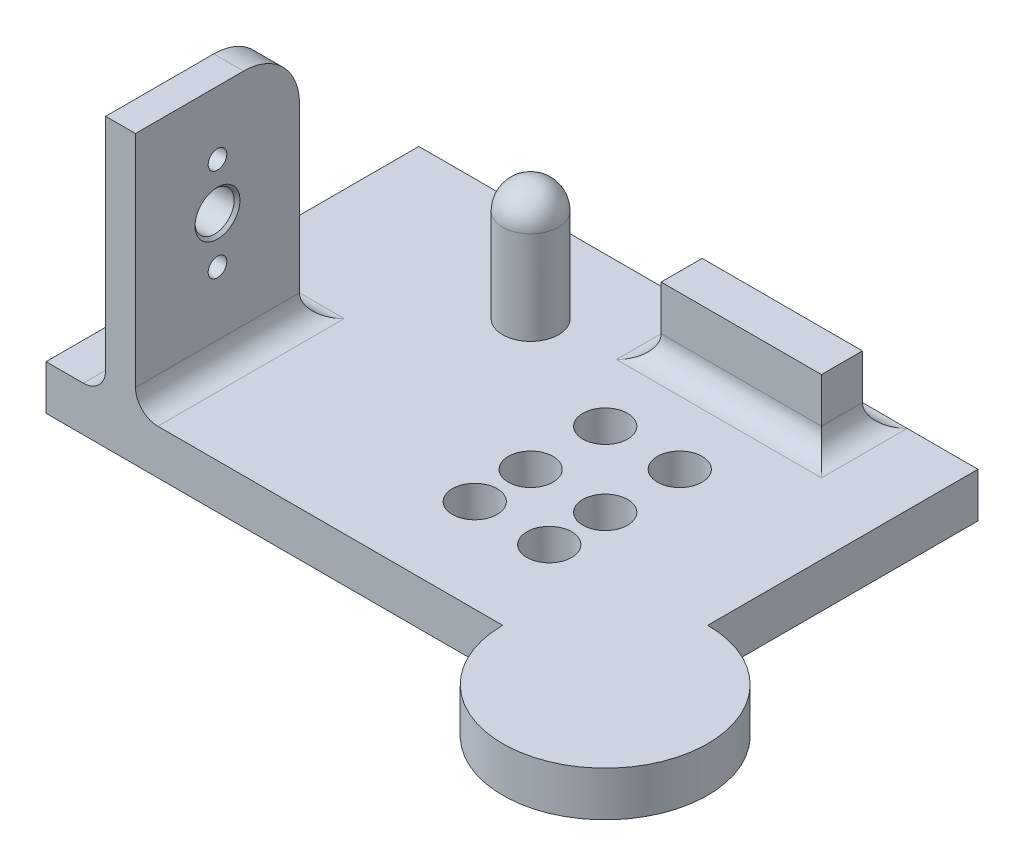
SolidWorks part; units mm, degrees
ref_plane "Front Plane" through (0, 0, 0) normal (0, 0, 1) x (1, 0, 0)
ref_plane "Top Plane" through (0, 0, 0) normal (0, 1, 0) x (1, 0, 0)
ref_plane "Right Plane" through (0, 0, 0) normal (1, 0, 0) x (0, 0, -1)
sketch "Sketch1" plane through (0, 0, 0) normal (0, 1, 0) x (1, 0, 0)
  line L1 (0, 0) -> (150, 0)
  line L2 (0, 0) -> (0, 100)
  line L3 (0, 100) -> (150, 100)
  line L4 (150, 0) -> (150, 100)
  dimension "D1" = 100
  dimension "D2" = 150
extrude "Boss-Extrude1" add sketch "Sketch1" along normal blind 12
sketch "Sketch2" plane through (0, 12, 0) normal (0, 1, 0) x (1, 0, 0)
  line L0 (0, 0) -> (150, 0) construction
  line L1 (16, 0) -> (24, 0)
  line L2 (16, 0) -> (16, 44)
  line L3 (16, 44) -> (24, 44)
  line L4 (24, 0) -> (24, 44)
  line L5 (0, 100) -> (0, 0) construction
  dimension "D1" = 16
  dimension "D2" = 8
  dimension "D3" = 44
extrude "Boss-Extrude2" add sketch "Sketch2" along normal blind 65
fillet "Fillet1" radius 6 3 edges at (16, 12, -22) (20, 12, -44) (24, 12, -22)
sketch "Sketch3" plane through (24, 0, 0) normal (1, 0, 0) x (0, 0, -1)
  line L0 (0, 47.5) -> (44, 47.5) construction
  line L1 (0, 77) -> (29, 77)
  line L2 (0, 77) -> (0, 18)
  line L3 (0, 18) -> (44, 18)
  line L4 (44, 62) -> (44, 18)
  line L5 (22, 77) -> (22, 18) construction
  line L6 (29, 77) -> (44, 77)
  line L7 (44, 77) -> (44, 62)
  arc A0 (29, 77) -> (44, 62) centre (29, 62) cw
  point P10 (22, 60)
  point P11 (22, 47.5)
  point P12 (22, 35)
  line M11 (44, 18) -> (44, 77)
  line M12 (44, 77) -> (0, 77)
  dimension "D2" = 15
  dimension "D1" = 12.5
extrude "Cut-Extrude1" cut sketch "Sketch3" against normal through all contours A0 M12 M11 region at (24, 73.6495, -40.6495)
hole_wizard "Ø5.0 (5) Diameter Hole1" positions "Sketch4" profile "Sketch5" hole size "Ø5.0" standard "AS" end condition through all
sketch "Sketch4" plane through (24, 0, 0) normal (1, 0, 0) x (0, 0, -1)
  point P0 (22, 60)
  point P3 (22, 35)
sketch "Sketch5" plane through (24, 60, -22) normal (0, 1, 0) x (0, 0, -1)
  line L0 (0, 0) -> (0, 24)
  line L1 (0, 24) -> (2.5, 24)
  line L2 (2.5, 24) -> (2.5, 0)
  line L5 (2.5, 0) -> (0, 0)
  line L11 (0, -6.35) -> (0, 107.95) construction
  dimension "Thru Hole Dia." = 5
  dimension "Thru Hole Depth" = 24
hole_wizard "M12x1.5 Tapped Hole1" positions "Sketch6" profile "Sketch7" tap size "M12x1.5" standard "AS" end condition through all
sketch "Sketch6" plane through (24, 0, 0) normal (1, 0, 0) x (0, 0, -1)
  point P0 (22, 47.5)
sketch "Sketch7" plane through (24, 47.5, -22) normal (0, 1, 0) x (0, 0, -1)
  line L0 (0, 0) -> (0, 24)
  line L1 (0, 24) -> (5.25, 24)
  line L2 (5.25, 24) -> (5.25, 0.775)
  line L3 (5.25, 0.775) -> (6.025, 0)
  line L5 (6.025, 0) -> (0, 0)
  line L6 (-5.25, 0.775) -> (-6.025, 0) construction
  line L11 (0, -6.35) -> (0, 107.95) construction
  dimension "Thru Tap Drill Dia." = 10.5
  dimension "Thru Tap Drill Depth" = 24
  dimension "Near C'Sink Dia." = 12.05
  dimension "Near C'Sink Angle" = 90
cosmetic thread "Hole Thread1" parameters "D2"=12
sketch "Sketch8" plane through (0, 12, 0) normal (0, 1, 0) x (1, 0, 0)
  line L0 (0, 100) -> (0, 0) construction
  line L1 (150, 100) -> (0, 100) construction
  circle A0 centre (55, 75) radius 7.5
  dimension "D1" = 15
  dimension "D2" = 55
  dimension "D3" = 25
extrude "Boss-Extrude3" add sketch "Sketch8" along normal blind 25
sketch "Sketch9" plane through (0, 12, 0) normal (0, 1, 0) x (1, 0, 0)
  line L0 (150, 27.5) -> (150, 0)
  line L1 (150, 0) -> (122.5, 0)
  circle A0 centre (150, 0) radius 27.5
  line M6 (30, 0) -> (150, 0)
  line M7 (150, 0) -> (150, 100)
  dimension "D1" = 55
extrude "Boss-Extrude4" add sketch "Sketch9" against normal up to surface (12 mm away) contours A0 M6 M7 region at (153.8905, 12, 3.8905) up to face at (75, 0, -50)
sketch "Sketch10" plane through (0, 12, 0) normal (0, 1, 0) x (1, 0, 0)
  line L0 (110, 100) -> (110, 0) construction
  line L1 (150, 100) -> (0, 100) construction
  line L2 (30, 0) -> (122.5, 0) construction
  line L3 (0, 50) -> (150, 50) construction
  line L4 (0, 100) -> (0, 0) construction
  line L5 (150, 27.5) -> (150, 100) construction
  line L6 (90, 100) -> (90, 0) construction
  line L7 (90, 25) -> (110, 25) construction
  line L8 (90, 40) -> (110, 40) construction
  line L9 (90, 60) -> (110, 60) construction
  circle A0 centre (90, 60) radius 6
  circle A1 centre (110, 60) radius 6
  circle A2 centre (90, 40) radius 6
  circle A3 centre (110, 40) radius 6
  circle A4 centre (90, 25) radius 6
  circle A5 centre (110, 25) radius 6
  dimension "D3" = 12
  dimension "D5" = 10
  dimension "D1" = 40
  dimension "D2" = 20
  dimension "D4" = 10
  dimension "D6" = 15
extrude "Cut-Extrude2" cut sketch "Sketch10" against normal through all and the other way through all
sketch "Sketch11" plane through (0, 37, 0) normal (0, 1, 0) x (1, 0, 0)
  line L0 (55, 82.5) -> (55, 67.5) construction
  line L1 (55, 82.5) -> (55, 67.5)
  circle A0 centre (55, 75) radius 7.5 construction
  circle A1 centre (55, 75) radius 7.5 construction
  arc A2 (55, 67.5) -> (55, 82.5) centre (55, 75) ccw
revolve "Revolve1" add sketch "Sketch11" angle 180 about L1 region at (51.8169, 37, -75) reverse direction yes
sketch "Sketch12" plane through (0, 12, 0) normal (0, 1, 0) x (1, 0, 0)
  line L0 (150, 27.5) -> (150, 100) construction
  line L1 (82, 94) -> (125, 94)
  line L2 (82, 94) -> (82, 83)
  line L3 (82, 83) -> (125, 83)
  line L4 (125, 94) -> (125, 83)
  line L5 (150, 100) -> (0, 100) construction
  dimension "D1" = 11
  dimension "D2" = 25
  dimension "D3" = 6
  dimension "D4" = 43
extrude "Boss-Extrude5" add sketch "Sketch12" along normal blind 18
fillet "Fillet2" radius 6 4 edges at (82, 12, -88.5) (103.5, 12, -94) (125, 12, -88.5) (103.5, 12, -83)
